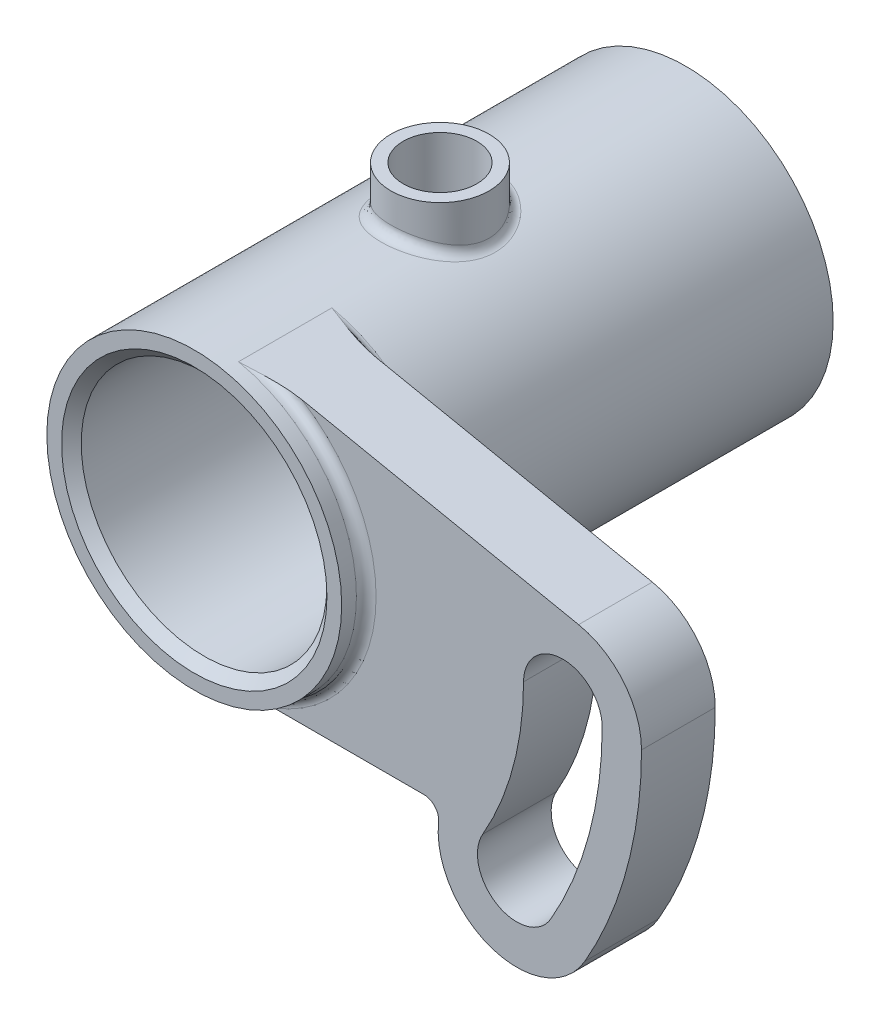
SolidWorks part; units mm, degrees
ref_plane "前视基准面" through (0, 0, 0) normal (0, 0, 1) x (1, 0, 0)
ref_plane "上视基准面" through (0, 0, 0) normal (0, 1, 0) x (1, 0, 0)
ref_plane "右视基准面" through (0, 0, 0) normal (1, 0, 0) x (0, 0, -1)
other "Configuration Table"
sketch "草图1" plane through (0, 0, 0) normal (0, 0, 1) x (1, 0, 0)
  circle A0 centre (0, 0) radius 30
  dimension "D1" = 60
extrude "凸台-拉伸1" add sketch "草图1" along normal blind 100
sketch "草图2" plane through (0, 0, 0) normal (0, 0, 1) x (1, 0, 0)
  circle A0 centre (0, 0) radius 25
  dimension "D1" = 50
extrude "切除-拉伸1" cut sketch "草图2" against normal through all both and the other way through all
sketch "草图3" plane through (0, 0, 0) normal (0, 0, 1) x (1, 0, 0)
  line L0 (0, 0) -> (-80.366, 0) construction
  line L1 (0, 0) -> (0, -61.2852) construction
  line L2 (0, 0) -> (-57.3412, -57.3412) construction
  line L3 (17.1291, -24.6291) -> (-51.4354, -72.3146)
  line L4 (-24.6291, 17.1291) -> (-72.3146, -51.4354)
  arc A2 (-72.3146, -51.4354) -> (-51.4354, -72.3146) centre (-60, -60) ccw
  circle A3 centre (0, 0) radius 30 construction
  circle A4 centre (0, 0) radius 30 construction
  arc A5 (17.1291, -24.6291) -> (-24.6291, 17.1291) centre (0, 0) cw
  point P11 (17.1291, -24.6291)
  point P15 (-18.9794, 23.2332)
  point P16 (17.1291, -24.6291)
  dimension "D3" = 30
  dimension "D1" = 45
  dimension "D2" = 60
extrude "凸台-拉伸2" add sketch "草图3" along normal blind 15 from offset 10
ref_plane "基准面1" through (0, 0, 25) normal (0, 0, 1) x (1, 0, 0)
sketch "草图4" plane through (0, 0, 25) normal (0, 0, 1) x (1, 0, 0)
  arc A0 (-72.3146, -51.4354) -> (-51.4354, -72.3146) centre (-60, -60) ccw construction
  arc A1 (-72.3146, -51.4354) -> (-51.4354, -72.3146) centre (-60, -60) ccw construction
  circle A2 centre (-60, -60) radius 15
  circle A3 centre (-60, -60) radius 10
  dimension "D1" = 20
extrude "凸台-拉伸3" add sketch "草图4" along normal blind 5 and the other way blind 25
sketch "草图5" plane through (0, 0, 25) normal (0, 0, 1) x (1, 0, 0)
  circle A0 centre (-60, -60) radius 10 construction
  circle A1 centre (-60, -60) radius 10
extrude "切除-拉伸2" cut sketch "草图5" against normal through all both and the other way through all contours A1
ref_plane "基准面2" through (0, 0, 100) normal (0, 0, 1) x (1, 0, 0)
sketch "草图6" plane through (0, 0, 100) normal (0, 0, 1) x (1, 0, 0)
  line L0 (0, 0) -> (88.6661, 0) construction
  line L1 (0, 0) -> (0, -71.2068) construction
  line L2 (0, 0) -> (78.8045, -45.4978) construction
  line L3 (0, -30) -> (41.7273, -30)
  line L4 (73.2, 15.6767) -> (6, 29.3939)
  arc A0 (70, 0) -> (60.6218, -35) centre (0, 0) cw construction
  arc A1 (70, 0) -> (60.6218, -35) centre (0, 0) cw construction
  arc A2 (67.55, -39) -> (78, 0) centre (0, 0) ccw
  arc A3 (53.6936, -31) -> (62, 0) centre (0, 0) ccw
  arc A4 (53.6936, -31) -> (67.55, -39) centre (60.6218, -35) ccw
  arc A5 (78, 0) -> (62, 0) centre (70, 0) ccw
  arc A6 (70, 0) -> (60.6218, -35) centre (0, 0) cw construction
  arc A7 (74.4782, -43) -> (86, 0) centre (0, 0) ccw
  arc A9 (44.7107, -33.3158) -> (74.4782, -43) centre (60.6218, -35) ccw
  arc A10 (86, 0) -> (73.2, 15.6767) centre (70, 0) ccw
  circle A11 centre (0, 0) radius 30 construction
  arc A12 (0, -30) -> (6, 29.3939) centre (0, 0) ccw
  arc A13 (44.7107, -33.3158) -> (41.7273, -30) centre (41.7273, -33) ccw
  point P8 (67.6148, -18.1173)
  point P13 (62.7294, -31)
  point P16 (67.6148, -18.1173)
  point P19 (52.6218, -45.4978)
  dimension "D3" = 8
  dimension "D4" = 16
  dimension "D5" = 3
  dimension "D1" = 30
  dimension "D2" = 70
extrude "凸台-拉伸4" add sketch "草图6" against normal blind 15 from offset 5 offset against normal yes
ref_plane "基准面3" through (0, 30, 0) normal (0, 1, 0) x (1, 0, 0)
sketch "草图7" plane through (0, 30, 0) normal (0, 1, 0) x (1, 0, 0)
  line L0 (30, 0) -> (-30, -100) construction
  line L1 (30, -100) -> (-30, 0) construction
  circle A0 centre (0, -50) radius 10
  dimension "D1" = 20
extrude "凸台-拉伸5" add sketch "草图7" along normal blind 8 and the other way blind 5
sketch "草图8" plane through (0, 30, 0) normal (0, 1, 0) x (1, 0, 0)
  circle A0 centre (0, -50) radius 7.5
  dimension "D1" = 15
extrude "切除-拉伸3" cut sketch "草图8" against normal blind 8 and the other way through all
fillet "圆角1" radius 2 1 edges at (1.6994, 29.9518, 40.1455)
chamfer "倒角2" distance 2 angle 45 1 edges at (25, 0, 0)
chamfer "倒角3" distance 2 angle 45 1 edges at (25, 0, 100)
fillet "圆角3" radius 2 4 edges at (-21.2132, -21.2132, 25) (-21.2132, -21.2132, 10) (-49.3934, -49.3934, 10) (-49.3934, -49.3934, 25)
fillet "圆角4" radius 2 2 edges at (29.8481, -3.0153, 80) (29.8481, -3.0153, 95)
surface "曲面-缝合1"
